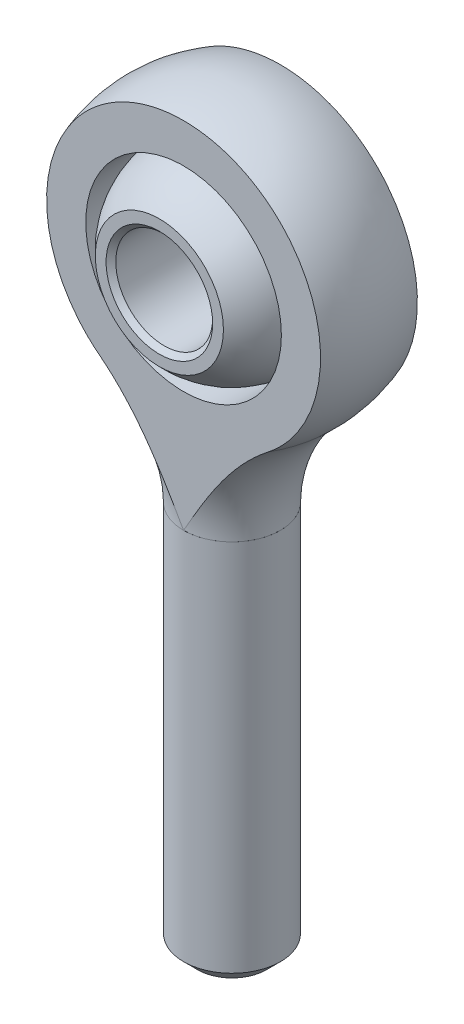
SolidWorks part; units mm, degrees
ref_plane "Front" through (0, 0, 0) normal (0, 0, 1) x (1, 0, 0)
ref_plane "Top" through (0, 0, 0) normal (0, 1, 0) x (1, 0, 0)
ref_plane "Right" through (0, 0, 0) normal (1, 0, 0) x (0, 0, -1)
sketch "Sketch1" plane through (0, 0, 0) normal (0, 0, 1) x (1, 0, 0)
  line L0 (0, 0) -> (0, -25.4)
  line L1 (0, -25.4) -> (3.175, -25.4)
  line L2 (3.175, -25.4) -> (3.175, 0)
  line L3 (3.175, 0) -> (0, 0)
  line L5 (0, 23.8125) -> (0, 0) construction
  line L6 (0, 23.8125) -> (9.525, 23.8125) construction
  line L7 (9.525, 23.8125) -> (9.525, 14.2875) construction
  line L8 (-3.175, -25.4) -> (-3.175, 0) construction
  line L9 (3.2732, -25.3433) -> (3.2732, -26.2501)
  line L10 (3.2732, -26.2501) -> (2.4879, -25.7967)
  line L11 (2.586, -25.8534) -> (2.586, -25.74)
  line L12 (2.4879, -25.7967) -> (3.2732, -25.3433)
  line L13 (3.2241, -25.3717) -> (3.2241, -26.2218)
  line L14 (3.2732, -25.7967) -> (3.175, -25.7967)
  line L15 (3.175, -25.4) -> (3.175, -26.1934)
  line L16 (2.4879, -25.7967) -> (2.586, -25.7967)
  arc A0 (6.3827, 7.2174) -> (0, 23.8125) centre (0, 14.2875) ccw construction
  circle A1 centre (0, 14.2875) radius 3.175 construction
  circle A2 centre (0, 14.2875) radius 6.35 construction
  circle A3 centre (0, 14.2875) radius 6.4135 construction
  arc A4 (3.175, 0) -> (6.3827, 7.2174) centre (12.8984, 0) cw construction
  point P24 (0, 20.6375)
  point P26 (3.175, -25.7967)
  point P28 (3.2241, -25.7967)
  dimension "A" = 6.35
  dimension "Ball Dia" = 12.7
  dimension "B" = 19.05
  dimension "D1" = 12.827
  dimension "D" = 39.6875
  dimension "E" = 25.4
  dimension "Thread Dia" = 6.35
  dimension "D2" = 60
  dimension "Pitch" = 0.9068
  dimension "D4" = 0.1133
sketch "Sketch2" plane through (0, 0, 0) normal (1, 0, 0) x (0, 0, -1)
  line L0 (3.175, 14.2875) -> (-3.175, 14.2875)
  line L1 (3.175, 15.0498) -> (0, 14.2875) construction
  line L2 (3.175, 13.5252) -> (0, 14.2875) construction
  line L6 (4.7625, 14.2875) -> (-4.7625, 14.2875)
  line L7 (0, 11.1125) -> (0, 17.4625)
  line L8 (0, 23.8125) -> (0, 0) construction
  line L9 (0, 17.4625) -> (0, 11.1125) construction
  circle A0 centre (0, 14.2875) radius 6.35
  circle A1 centre (0, 14.2875) radius 9.525
  point P4 (0, 14.2875)
  point P7 (0, 20.6375)
  point P9 (0, 7.9375)
  point P14 (0, 14.2875)
  point P18 (0, 14.2875)
  point P23 (9.525, 14.2875)
  point P25 (-9.525, 14.2875)
  dimension "OAWidth" = 6.35
  dimension "Swivel" = 27
  dimension "BallWidth" = 9.525
sketch "Sketch15" plane through (0, 0, 0) normal (0, 0, 1) x (1, 0, 0)
  line L0 (0, 23.8125) -> (0, 0) construction
  line L1 (9.525, 23.8125) -> (-9.525, 23.8125)
  line L2 (9.525, 23.8125) -> (9.525, 0)
  line L3 (9.525, 0) -> (-9.525, 0)
  line L4 (-9.525, 23.8125) -> (-9.525, 0)
  line L5 (3.175, 0) -> (0, 0) construction
  point P5 (0, 23.8125)
sketch "Sketch14" plane through (0, 0, 0) normal (0, 0, 1) x (1, 0, 0)
  line L1 (0, 0) -> (0, -25.4) construction
  line L2 (0, -25.4) -> (3.175, -25.4) construction
  line L3 (3.175, -25.4) -> (3.175, 0) construction
  line L5 (0, 0) -> (0, -25.4)
  line L6 (0, -25.4) -> (3.175, -25.4)
  line L7 (3.175, -25.4) -> (3.175, 0)
  line L8 (3.175, 0) -> (0, 0) construction
  line L9 (3.175, 0) -> (0, 0)
revolve "Revolve4" add sketch "Sketch14" angle 360 about L0
sketch "Sketch21" plane through (0, 0, 0) normal (0, 0, 1) x (1, 0, 0)
  line L0 (0, 23.8125) -> (0, 0) construction
  line L1 (3.175, 0) -> (0, 0) construction
  line L2 (0, 23.8125) -> (0, 0)
  line L3 (3.175, 0) -> (0, 0)
  arc A0 (6.3827, 7.2174) -> (3.175, 0) centre (12.8984, 0) ccw construction
  arc A1 (6.3827, 7.2174) -> (0, 23.8125) centre (0, 14.2875) ccw construction
  arc A2 (6.3827, 7.2174) -> (3.175, 0) centre (12.8984, 0) ccw
  arc A3 (6.3827, 7.2174) -> (0, 23.8125) centre (0, 14.2875) ccw
revolve "Revolve5" add sketch "Sketch21" angle 360 about L0
sketch "Sketch24" plane through (0, 0, 0) normal (1, 0, 0) x (0, 0, -1)
  line L0 (3.175, 14.2875) -> (3.175, 23.8125)
  line L1 (3.175, 23.8125) -> (9.525, 23.8125)
  line L2 (9.525, 0) -> (9.525, 23.8125)
  line L3 (3.175, 14.2875) -> (3.175, 0.635)
  line L4 (3.175, 0.635) -> (3.175, 0)
  line L5 (3.175, 0) -> (9.525, 0)
  line L6 (0, 23.8125) -> (0, 0) construction
  line L7 (0, 23.8125) -> (0, 0) construction
  line L8 (-3.175, 0) -> (-9.525, 0)
  line L9 (-3.175, 0.635) -> (-3.175, 0)
  line L10 (-3.175, 14.2875) -> (-3.175, 0.635)
  line L11 (-9.525, 0) -> (-9.525, 23.8125)
  line L12 (-3.175, 23.8125) -> (-9.525, 23.8125)
  line L13 (-3.175, 14.2875) -> (-3.175, 23.8125)
  dimension "D1" = 0.635
extrude "Cut-Extrude10" cut sketch "Sketch24" against normal through all both and the other way through all
sketch "Sketch17" plane through (0, 0, 0) normal (0, 0, 1) x (1, 0, 0)
  circle A2 centre (0, 14.2875) radius 6.4135 construction
  circle A3 centre (0, 14.2875) radius 6.4135
extrude "Cut-Extrude9" cut sketch "Sketch17" against normal through all both and the other way through all
sketch "Sketch7" plane through (0, 0, 0) normal (0, 0, 1) x (1, 0, 0)
  line L0 (0, 20.6375) -> (0, 7.9375)
  line L1 (0, 23.8125) -> (0, 0) construction
  line L2 (0, 0) -> (0, 7.9375) construction
  arc A0 (0, 7.9375) -> (0, 20.6375) centre (0, 14.2875) ccw
  circle A1 centre (0, 14.2875) radius 6.35 construction
revolve "Revolve3" add sketch "Sketch7" angle 360 about L2
sketch "Sketch10" plane through (0, 0, 0) normal (0, 0, 1) x (1, 0, 0)
  circle A0 centre (0, 14.2875) radius 3.175 construction
  circle A1 centre (0, 14.2875) radius 3.175
extrude "Cut-Extrude4" cut sketch "Sketch10" against normal through all and the other way through all
sketch "Sketch22" plane through (0, 0, 0) normal (0, 0, 1) x (1, 0, 0)
  line L0 (-9.525, 23.8125) -> (-9.525, 0) construction
  line L1 (9.525, 0) -> (-9.525, 0) construction
  line L2 (9.525, 23.8125) -> (9.525, 0) construction
  line L3 (9.525, 23.8125) -> (-9.525, 23.8125) construction
  line L4 (-9.525, 23.8125) -> (-9.525, 0)
  line L5 (9.525, 0) -> (-9.525, 0)
  line L6 (9.525, 23.8125) -> (9.525, 0)
  line L7 (9.525, 23.8125) -> (-9.525, 23.8125)
extrude "Cut-Extrude7" cut sketch "Sketch22" against normal through all from vertex starting at point (0, 14.2875, -4.7625)
sketch "Sketch23" plane through (0, 0, 0) normal (0, 0, 1) x (1, 0, 0)
  line L0 (-9.525, 23.8125) -> (-9.525, 0) construction
  line L1 (9.525, 0) -> (-9.525, 0) construction
  line L2 (9.525, 23.8125) -> (9.525, 0) construction
  line L3 (9.525, 23.8125) -> (-9.525, 23.8125) construction
  line L4 (-9.525, 23.8125) -> (-9.525, 0)
  line L5 (9.525, 0) -> (-9.525, 0)
  line L6 (9.525, 23.8125) -> (9.525, 0)
  line L7 (9.525, 23.8125) -> (-9.525, 23.8125)
extrude "Cut-Extrude8" cut sketch "Sketch23" along normal through all from vertex starting at point (0, 14.2875, 4.7625)
chamfer "Chamfer1" distance 0.9068 angle 45 1 edges at (-3.175, -25.4, 0)
chamfer "Chamfer2" distance 0.3175 angle 45 2 edges at (3.175, 14.2875, 4.7625) (3.175, 14.2875, -4.7625)
sketch "Sketch18" [suppressed] plane through (0, -25.4, 0) normal (0, -1, 0) x (1, 0, 0)
  circle A0 centre (0, 0) radius 3.175 construction
  circle A1 centre (0, 0) radius 3.175
curve "Helix/Spiral1" [suppressed] pitch 0.9068 height 26.3068 turns 29.0112
sketch "Sketch19" [suppressed] plane through (0, 0, 0) normal (0, 0, 1) x (1, 0, 0)
  line L0 (2.586, -25.8534) -> (2.586, -25.74) construction
  line L1 (2.4879, -25.7967) -> (3.2732, -25.3433) construction
  line L2 (3.2732, -26.2501) -> (2.4879, -25.7967) construction
  line L3 (3.2241, -25.3717) -> (3.2241, -26.2218) construction
  line L4 (2.586, -25.8534) -> (2.586, -25.74)
  line L5 (2.586, -25.74) -> (3.2241, -25.3717)
  line L6 (3.2241, -26.2218) -> (2.586, -25.8534)
  line L7 (3.2241, -25.3717) -> (3.2241, -26.2218)
sweep "Cut-Sweep1" [suppressed] cut profiles "Sketch19" path "Helix/Spiral1"
ref_plane "Plane1" [suppressed] through (0, 0, 0) normal (0, 1, 0) x (1, 0, 0)
sketch "Sketch20" [suppressed] plane through (0, 0, 0) normal (0, 1, 0) x (1, 0, 0)
  circle A0 centre (0, 0) radius 3.175
extrude "Boss-Extrude2" [suppressed] add sketch "Sketch20" against normal through all draft 60
combine bodies "Combine1" [suppressed] operation type add bodies to combine 130 133
sketch "Sketch25" plane through (0, 0, 0) normal (0, 0, 1) x (1, 0, 0)
  line L0 (0, -25.4) -> (0, 14.2875)
  line L1 (-2.2682, -25.4) -> (2.2682, -25.4) construction
  line L2 (0, -25.4) -> (0, -7.62)
  dimension "D1" = 17.78
move or copy body "Body-Move/Copy1" [suppressed] bodies to move or copy 122 132 133 parameters "D1"=0, "D2"=0, "D3"=0
move or copy body "Body-Move/Copy2" [suppressed] bodies to move or copy 136 137 138 parameters "D1"=0, "D2"=0, "D3"=0
move or copy body "Body-Move/Copy3" [suppressed] bodies to move or copy 139 140 141 parameters "D1"=0, "D2"=0, "D3"=0
move or copy body "Body-Move/Copy4" [suppressed] bodies to move or copy 142 143 144 parameters "D1"=0, "D2"=0, "D3"=0
move or copy body "Body-Move/Copy5" [suppressed] bodies to move or copy 145 146 147 parameters "D1"=0, "D2"=0, "D3"=0
move or copy body "Body-Move/Copy6" [suppressed] bodies to move or copy 148 149 150 parameters "D1"=0, "D2"=0, "D3"=0
move or copy body "Body-Move/Copy7" [suppressed] bodies to move or copy 151 152 153 parameters "D1"=0, "D2"=0, "D3"=0
move or copy body "Body-Move/Copy8" [suppressed] bodies to move or copy 154 155 156 parameters "D1"=0, "D2"=0, "D3"=0
equation "\"D1@Sketch1\"=\"Ball Dia@Sketch1\"*1.01"
equation "\"D1\"= \"A@Sketch1\" / 20"
equation "\"D3\"= \"E@Sketch1\" + .2"
equation "\"D4@Sketch1\"=\"Pitch@Sketch1\"/8"
equation "\"D1@Chamfer1\"=\"Pitch@Sketch1\""
equation "\"D4@Helix/Spiral1\"=\"Pitch@Sketch1\""
equation "\"D3@Helix/Spiral1\"=\"E@Sketch1\"+\"Pitch@Sketch1\""
equation "\"D1@Chamfer2\"=\"A@Sketch1\"/20"
equation "\"D1@Sketch24\"=(\"OAWidth@Sketch2\"/2)/5"
